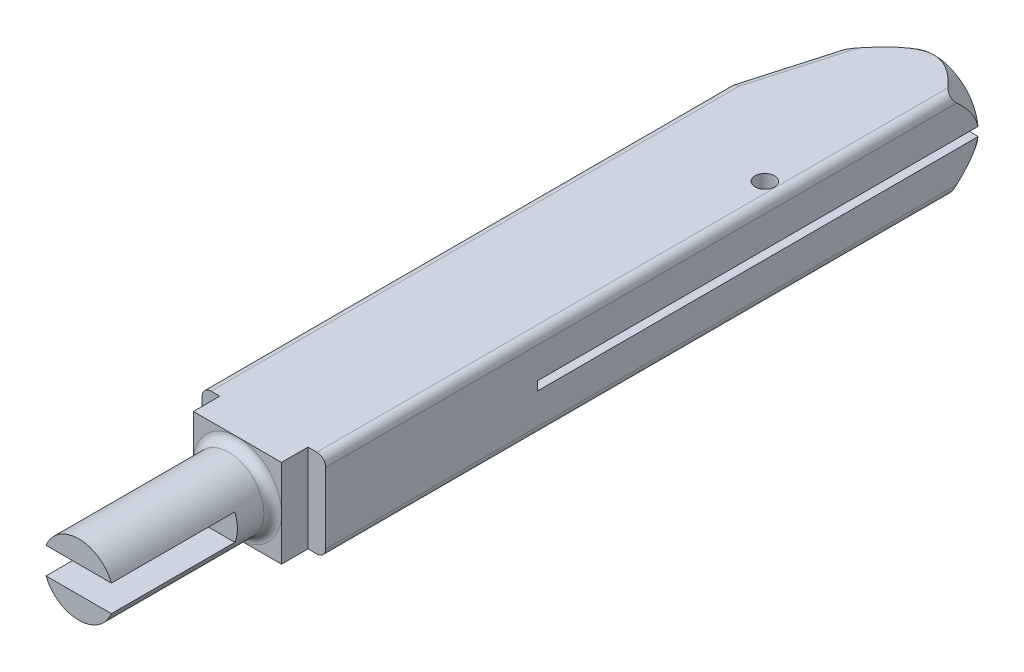
SolidWorks part; units mm, degrees
ref_plane "前视基准面" through (0, 0, 0) normal (0, 0, 1) x (1, 0, 0)
ref_plane "上视基准面" through (0, 0, 0) normal (0, 1, 0) x (1, 0, 0)
ref_plane "右视基准面" through (0, 0, 0) normal (1, 0, 0) x (0, 0, -1)
sketch "草图1" plane through (0, 0, 0) normal (0, 0, 1) x (1, 0, 0)
  line L1 (-3.5, -2.5) -> (3.5, -2.5)
  line L2 (-3.5, -2.5) -> (-3.5, 2.5)
  line L3 (-3.5, 2.5) -> (3.5, 2.5)
  line L4 (3.5, -2.5) -> (3.5, 2.5)
  line L5 (-3.5, -2.5) -> (3.5, 2.5) construction
  line L6 (-3.5, 2.5) -> (3.5, -2.5) construction
  point P0 (0, 0)
  dimension "D1" = 5
  dimension "D2" = 7
extrude "凸台-拉伸1" add sketch "草图1" along normal blind 37
sketch "草图2" plane through (0, 0, 37) normal (0, 0, 1) x (1, 0, 0)
  line L1 (2.5, -2.5) -> (-2.5, -2.5)
  line L2 (2.5, -2.5) -> (2.5, 2.5)
  line L3 (2.5, 2.5) -> (-2.5, 2.5)
  line L4 (-2.5, -2.5) -> (-2.5, 2.5)
  line L5 (2.5, -2.5) -> (-2.5, 2.5) construction
  line L6 (2.5, 2.5) -> (-2.5, -2.5) construction
  point P0 (0, 0)
  dimension "D1" = 5
  dimension "D2" = 5
extrude "凸台-拉伸2" add sketch "草图2" along normal blind 1.5
sketch "草图3" plane through (0, 0, 38.5) normal (0, 0, 1) x (1, 0, 0)
  circle A0 centre (0, 0) radius 2
  dimension "D1" = 4
extrude "凸台-拉伸3" add sketch "草图3" along normal blind 9
sketch "草图4" plane through (0, 0, 47.5) normal (0, 0, 1) x (1, 0, 0)
  line L1 (-7.3396, -0.75) -> (7.3396, -0.75)
  line L2 (-7.3396, -0.75) -> (-7.3396, 0.75)
  line L3 (-7.3396, 0.75) -> (7.3396, 0.75)
  line L4 (7.3396, -0.75) -> (7.3396, 0.75)
  line L5 (-7.3396, -0.75) -> (7.3396, 0.75) construction
  line L6 (-7.3396, 0.75) -> (7.3396, -0.75) construction
  point P0 (0, 0)
  point P6 (0, 0)
  dimension "D1" = 1.5
extrude "切除-拉伸1" cut sketch "草图4" against normal blind 7
sketch "草图5" plane through (0, 2.5, 0) normal (0, 1, 0) x (1, 0, 0)
  line L0 (-3.5, 0) -> (-3.5, -7)
  line L1 (-3.5, -37) -> (-3.5, 0) construction
  line L2 (-3.5, -7) -> (-1.5, 0)
  line L3 (3.5, 0) -> (-3.5, 0) construction
  line L4 (-1.5, 0) -> (-3.5, 0)
  line L5 (3.5, -37) -> (3.5, 0) construction
  dimension "D1" = 5
  dimension "D2" = 7
extrude "切除-拉伸2" cut sketch "草图5" against normal through all contours L4 L0 L2
sketch "草图6" plane through (0, 0, 0) normal (0, 0, -1) x (-1, 0, 0)
  line L1 (-6.7984, -0.25) -> (6.7984, -0.25)
  line L2 (-6.7984, -0.25) -> (-6.7984, 0.25)
  line L3 (-6.7984, 0.25) -> (6.7984, 0.25)
  line L4 (6.7984, -0.25) -> (6.7984, 0.25)
  line L5 (-6.7984, -0.25) -> (6.7984, 0.25) construction
  line L6 (-6.7984, 0.25) -> (6.7984, -0.25) construction
  point P0 (0, 0)
  dimension "D1" = 0.5
extrude "切除-拉伸3" cut sketch "草图6" against normal blind 25 contours L2 L1 L4 L3
sketch "草图7" plane through (0, 0, 0) normal (0, 0, -1) x (-1, 0, 0)
  line L0 (-3.5, 0.25) -> (-3.5, 2.5) construction
  circle A0 centre (-1, 0) radius 2.5
  dimension "D1" = 5
  dimension "D2" = 2.5
extrude "切除-拉伸7" cut sketch "草图7" against normal blind 5 draft 30 flip side to cut contours A0
sketch "草图8" plane through (0, 0, 0) normal (0, 0, -1) x (-1, 0, 0)
  circle A0 centre (-1, 0) radius 1
  dimension "D1" = 2
extrude "切除-拉伸8" cut sketch "草图8" against normal blind 15 contours A0
fillet "圆角1" radius 0.5 6 edges at (-2.9096, -2.5, 4.9336) (-2.9096, 2.5, 4.9336) (3.5, -2.5, 19.3968) (3.5, 2.5, 19.3968) (-3.5, -2.5, 22) (-3.5, 2.5, 22)
fillet "圆角2" radius 0.5 1 edges at (2, 0, 38.5)
sketch "草图9" plane through (0, 2.5, 0) normal (0, 1, 0) x (1, 0, 0)
  line L0 (3, -37) -> (3, -1.2151) construction
  circle A0 centre (2.4, -11) radius 0.55
  point P5 (3, -12.1789)
  dimension "D1" = 1.1
  dimension "D2" = 2
  dimension "D3" = 0.6
extrude "切除-拉伸9" cut sketch "草图9" against normal through all
chamfer "倒角1" distance 0.5 angle 45 1 edges at (2.4, -2.5, 11.55)
